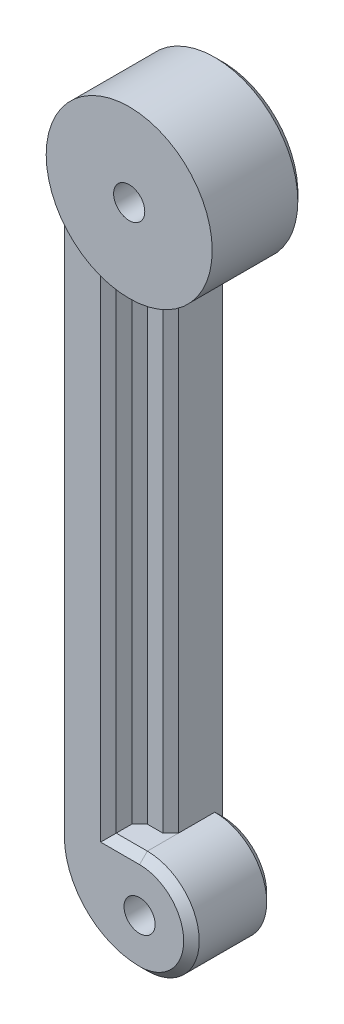
SolidWorks part; units mm, degrees
ref_plane "Front Plane" through (0, 0, 0) normal (0, 0, 1) x (1, 0, 0)
ref_plane "Top Plane" through (0, 0, 0) normal (0, 1, 0) x (1, 0, 0)
ref_plane "Right Plane" through (0, 0, 0) normal (1, 0, 0) x (0, 0, -1)
sketch "Sketch1" plane through (0, 0, 0) normal (0, 0, 1) x (1, 0, 0)
  line L0 (0, 0) -> (0, 60) construction
  line L1 (-8, 3) -> (-8, 60)
  line L3 (0, 5) -> (0, 52)
  arc A1 (0, 52) -> (-8, 60) centre (0, 60) ccw
  circle A2 centre (0, 60) radius 1.5
  circle A3 centre (0, 0) radius 1.5
  arc A4 (0, -5) -> (0, 5) centre (0, 0) ccw
  arc A5 (-8, 3) -> (0, -5) centre (0, 3) ccw
  point P3 (0, 30)
  dimension "D1" = 3
  dimension "D3" = 8
  dimension "D4" = 5
  dimension "D2" = 60
extrude "Boss-Extrude1" add sketch "Sketch1" along normal blind 5
sketch "Sketch2" plane through (0, 0, 5) normal (0, 0, 1) x (1, 0, 0)
  circle A0 centre (0, 60) radius 8
  circle A1 centre (0, 60) radius 1.5
extrude "Boss-Extrude2" add sketch "Sketch2" along normal blind 4
sketch "Sketch3" plane through (0, 0, 5) normal (0, 0, 1) x (1, 0, 0)
  line L1 (-8, 3) -> (-8, 60)
  line L2 (-8, 60) -> (-3, 55.3716)
  line L3 (-3, 55.3716) -> (-3, 5)
  line L4 (-8, 60) -> (-8, 3) construction
  line L6 (-3, 5) -> (0, 5)
  line L7 (0, 5) -> (0, 52) construction
  arc A3 (-8, 3) -> (0, -5) centre (0, 3) ccw
  arc A4 (-8, 3) -> (0, -5) centre (0, 3) ccw construction
  circle A7 centre (0, 0) radius 1.5
  arc A8 (0, 5) -> (0, -5) centre (0, 0) cw
  dimension "D1" = 5
extrude "Boss-Extrude3" add sketch "Sketch3" along normal blind 3
sketch "Sketch4" plane through (0, 0, 0) normal (0, 0, -1) x (-1, 0, 0)
  line L1 (3.1754, 60) -> (1.5877, 62.75)
  line L2 (1.5877, 62.75) -> (-1.5877, 62.75)
  line L3 (-1.5877, 62.75) -> (-3.1754, 60)
  line L4 (-3.1754, 60) -> (-1.5877, 57.25)
  line L5 (-1.5877, 57.25) -> (1.5877, 57.25)
  line L6 (1.5877, 57.25) -> (3.1754, 60)
  line L7 (3.1754, 0) -> (1.5877, 2.75)
  line L8 (1.5877, 2.75) -> (-1.5877, 2.75)
  line L9 (-1.5877, 2.75) -> (-3.1754, 0)
  line L10 (-3.1754, 0) -> (-1.5877, -2.75)
  line L11 (-1.5877, -2.75) -> (1.5877, -2.75)
  line L12 (1.5877, -2.75) -> (3.1754, 0)
  circle A0 centre (0, 60) radius 2.75 construction
  circle A1 centre (0, 0) radius 2.75 construction
  dimension "D1" = 5.5
extrude "Cut-Extrude1" cut sketch "Sketch4" against normal blind 2.5
chamfer "Chaflán1" distance 0.75 angle 45 4 edges at (5, 0, 0) (-5.6569, -2.6569, 0) (-8, 31.5, 0) (5.6569, 65.6569, 0)
chamfer "Chaflán2" distance 0.75 angle 45 4 edges at (-1.5, 5, 8) (-8, 31.5, 8) (5, 0, 8) (-5.6569, -2.6569, 8)
chamfer "Chaflán3" distance 0.75 angle 45 3 edges at (-3, 28.4169, 8) (-3, 28.7919, 5) (0, 28.5, 5)
